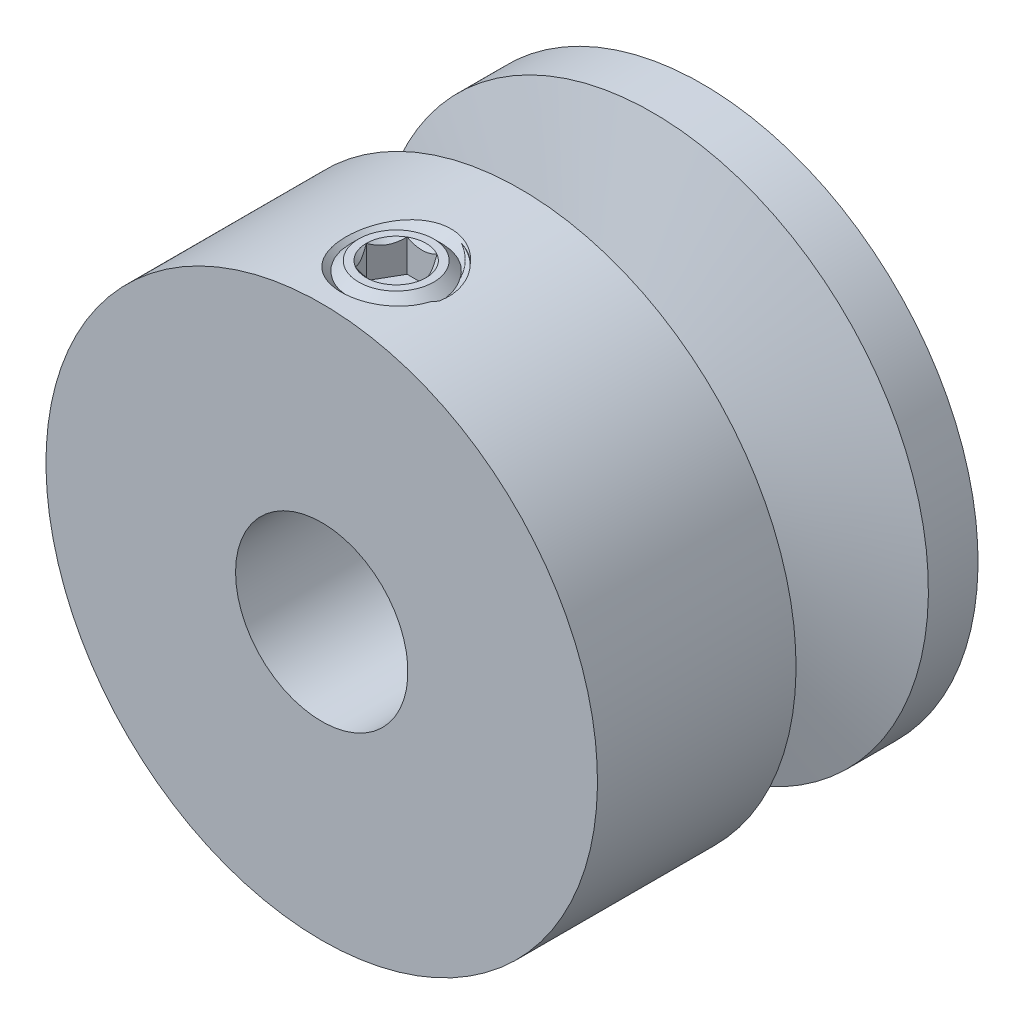
SolidWorks part; units mm, degrees
ref_plane "Front Plane" through (0, 0, 0) normal (0, 0, 1) x (1, 0, 0)
ref_plane "Top Plane" through (0, 0, 0) normal (0, 1, 0) x (1, 0, 0)
ref_plane "Right Plane" through (0, 0, 0) normal (1, 0, 0) x (0, 0, -1)
sketch "Sketch1" plane through (0, 0, 0) normal (1, 0, 0) x (0, 0, -1)
  line L0 (-12.192, 0) -> (5.334, 0) construction
  line L1 (-3.048, 12.7) -> (3.048, 12.7) construction
  line L4 (-12.192, 12.7) -> (-3.048, 12.7)
  line L5 (-12.192, 12.7) -> (5.334, 12.7) construction
  line L9 (5.334, 0) -> (5.334, 12.7)
  line L10 (5.334, 12.7) -> (3.048, 12.7)
  line L12 (5.334, 12.7) -> (5.334, 0) construction
  line L13 (-3.048, 12.7) -> (-1.2272, 6.35)
  line L14 (-1.2272, 6.35) -> (1.2272, 6.35)
  line L15 (1.2272, 6.35) -> (3.048, 12.7)
  line L16 (5.334, 3.9688) -> (-12.192, 3.9687) construction
  line L17 (0, 12.7) -> (0, 0) construction
  line L18 (-12.192, 12.7) -> (-12.192, 0)
  line L21 (5.334, 0) -> (-12.192, 0)
  line L22 (5.334, 11.43) -> (-12.192, 11.43) construction
  point P16 (0, 6.35)
  dimension "D1" = 9.144
  dimension "A" = 32
  dimension "OD" = 25.4
  dimension "Bore" = 7.9375
  dimension "Width" = 17.526
  dimension "X" = 8.382
  dimension "PD" = 22.86
  dimension "W" = 6.096
  dimension "Depth" = 6.35
revolve "Revolve1" add sketch "Sketch1" angle 360 about L0
sketch "Sketch2" plane through (0, 0, -5.334) normal (0, 0, -1) x (-1, 0, 0)
  circle A0 centre (0, 0) radius 3.9688
  circle A1 centre (0, 0) radius 11.43 construction
extrude "Cut-Extrude1" cut sketch "Sketch2" against normal up to vertex (17.526 mm away) up to point (0, 0, 12.192)
ref_plane "Plane1" through (0, 12.7, 0) normal (0, 1, 0) x (-1, 0, 0)
sketch "Sketch3" plane through (0, 12.7, 0) normal (0, 1, 0) x (-1, 0, 0)
  line L0 (0, 5.334) -> (0, 12.192) construction
  line L2 (0, -5.334) -> (0, 12.192) construction
  line L3 (0, -3.048) -> (0, -5.334) construction
  line L5 (0, 3.048) -> (0, 5.334) construction
  line L6 (0, 12.192) -> (0, 3.048) construction
  line L7 (0, 11.176) -> (0, 10.1177) construction
  circle A0 centre (0, 8.763) radius 2.413 construction
  circle A1 centre (0, 8.763) radius 1.7515
  dimension "D1" = 4.826
  dimension "D2" = 1.0583
  dimension "D3" = 0.6615
extrude "Cut-Extrude2" cut sketch "Sketch3" against normal up to surface (12.7 mm away) up to plane "Top Plane"
sketch "Sketch4" plane through (0, 12.7, 0) normal (0, 1, 0) x (-1, 0, 0)
  circle A0 centre (0, 8.763) radius 2.413 construction
  circle A1 centre (0, 8.763) radius 2.413
  point P3 (0, 11.176)
curve "Helix/Spiral1" pitch 1.0583 height 13.7583 radius 2.413 centre (0, 12.7, 8.763) axis (0, -1, 0) start towards (0, 0, 1)
sketch "Sketch5" plane through (0, 0, 0) normal (1, 0, 0) x (0, 0, -1)
  line L0 (-10.374, 13.7583) -> (-10.374, 12.7) construction
  line L1 (-10.374, 12.7) -> (-11.2906, 13.2292) construction
  line L2 (-11.2906, 13.2292) -> (-10.374, 13.7583) construction
  line L3 (-10.374, 12.7) -> (-11.176, 12.7) construction
  line L4 (-11.176, 12.7) -> (-11.176, 13.163) construction
  line L5 (-11.176, 13.163) -> (-11.176, 13.2953) construction
  line L6 (-10.4886, 12.7661) -> (-10.4886, 13.6922) construction
  line L7 (-11.2906, 13.2292) -> (-11.176, 13.2292) construction
  line L8 (-10.4886, 13.2292) -> (-10.374, 13.2292) construction
  line L9 (-10.4313, 13.7253) -> (-10.4313, 12.7331)
  line L10 (-10.4313, 12.7331) -> (-11.176, 13.163)
  line L11 (-11.176, 13.163) -> (-11.176, 13.2953)
  line L12 (-11.176, 13.2953) -> (-10.4313, 13.7253)
  point P16 (-10.4313, 13.2292)
  dimension "D1" = 1.0583
  dimension "D2" = 0.1323
sweep "Cut-Sweep1" cut profiles "Sketch5" path "Helix/Spiral1"
sketch "Sketch6" plane through (0, 12.7, 0) normal (0, 1, 0) x (-1, 0, 0)
  circle A0 centre (0, 8.763) radius 2.5276
extrude "Cut-Extrude3" cut sketch "Sketch6" against normal through all draft 45
sketch "Sketch7" plane through (0, 0, 0) normal (1, 0, 0) x (0, 0, -1)
  line L0 (-8.763, 12.7) -> (-8.763, 6.35) construction
  line L1 (-11.176, 7.0374) -> (-11.176, 12.0126)
  line L2 (-8.763, 12.7) -> (-11.176, 12.7) construction
  line L3 (-8.763, 12.7) -> (-8.763, 6.35)
  line L4 (-8.763, 6.35) -> (-11.176, 6.35) construction
  line L5 (-11.176, 12.7) -> (-11.176, 6.35) construction
  line L6 (-10.4886, 12.7) -> (-11.176, 12.0126)
  line L7 (-11.176, 7.0374) -> (-10.4886, 6.35)
  line L8 (-10.4886, 12.7) -> (-8.763, 12.7)
  line L9 (-10.4886, 6.35) -> (-8.763, 6.35)
  line L10 (-5.334, 12.7) -> (-12.192, 12.7) construction
  line L11 (-10.4886, 12.7) -> (-11.176, 12.7) construction
  line L12 (-11.176, 12.7) -> (-11.176, 12.0126) construction
  line L13 (-10.4886, 12.7661) -> (-10.4886, 13.6922) construction
  dimension "D1" = 6.35
revolve "Revolve2" add sketch "Sketch7" angle 360 about L0
sketch "Sketch8" plane through (0, 12.7, 0) normal (0, 1, 0) x (1, 0, 0)
  line L1 (1.3748, -8.763) -> (0.6874, -7.5724)
  line L2 (0.6874, -7.5724) -> (-0.6874, -7.5724)
  line L3 (-0.6874, -7.5724) -> (-1.3748, -8.763)
  line L4 (-1.3748, -8.763) -> (-0.6874, -9.9536)
  line L5 (-0.6874, -9.9536) -> (0.6874, -9.9536)
  line L6 (0.6874, -9.9536) -> (1.3748, -8.763)
  circle A0 centre (0, -8.763) radius 1.1906 construction
  dimension "D1" = 2.3813
extrude "Cut-Extrude4" cut sketch "Sketch8" against normal blind 1.4883
sketch "Sketch9" plane through (0, 12.7, 0) normal (0, 1, 0) x (1, 0, 0)
  circle A0 centre (0, -8.763) radius 1.3748
extrude "Cut-Extrude5" cut sketch "Sketch9" against normal through all draft 45
equation "\"D3@Sketch3\" = \"D2@Sketch3\" * 5 / 8"
equation "\"D4@Helix/Spiral1\" = \"D2@Sketch3\""
equation "\"D3@Helix/Spiral1\" = \"D4@Helix/Spiral1\" + ( \"OD@Sketch1\" / 2 ) "
equation "\"D1@Sketch5\" = \"D4@Helix/Spiral1\""
equation "\"D2@Sketch5\" = \"D1@Sketch5\" / 8"
